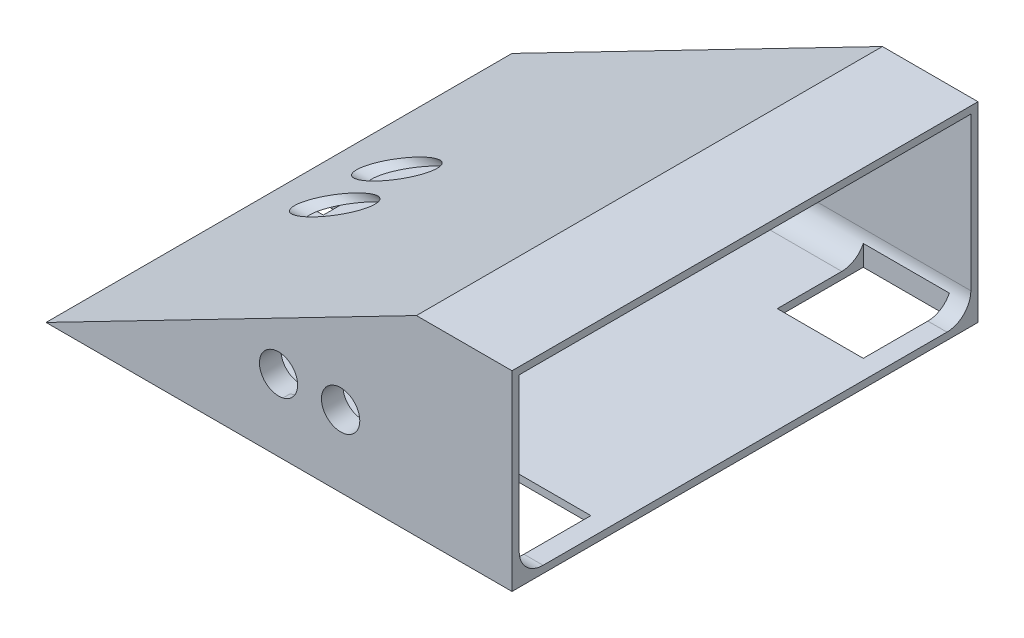
SolidWorks part; units mm, degrees
ref_plane "Front Plane" through (0, 0, 0) normal (0, 0, 1) x (1, 0, 0)
ref_plane "Top Plane" through (0, 0, 0) normal (0, 1, 0) x (1, 0, 0)
ref_plane "Right Plane" through (0, 0, 0) normal (1, 0, 0) x (0, 0, -1)
ref_plane "Plane1" through (0, 0, 0) normal (1, 0, 0) x (0, 0, -1)
ref_plane "Plane2" through (0, 0, 97.5) normal (0, 0, 1) x (1, 0, 0)
ref_plane "Plane3" through (75, 0, 0) normal (1, 0, 0) x (0, 0, -1)
sketch "Sketch2" plane through (0, 0, 0) normal (0, 0, 1) x (1, 0, 0)
  line L0 (0, 0) -> (195, 0)
  line L1 (195, 0) -> (195, 80)
  line L2 (195, 80) -> (155, 80)
  line L3 (155, 80) -> (0, 0)
  dimension "D1" = 195
  dimension "D2" = 40
  dimension "80" = 80
extrude "Robot" add sketch "Sketch2" along normal blind 195
sketch "Sketch3" plane through (0, 0, 195) normal (0, 0, 1) x (1, 0, 0)
  line L0 (0, 0) -> (195, 0) construction
  circle A0 centre (97.2899, 30) radius 8.02
  circle A1 centre (123.2899, 30) radius 8.02
  dimension "D1" = 30
  dimension "D2" = 16.04
  dimension "D4" = 16.04
  dimension "D3" = 26
  dimension "D5" = 30
sketch "Arriba" plane through (0, 80, 0) normal (0, 1, 0) x (1, 0, 0)
  line L0 (195, 0) -> (195, -195) construction
  line L1 (0, 0) -> (0, -195) construction
  line L2 (0, -97.5) -> (195, -97.5) construction
  line L3 (0, 0) -> (195, 0) construction
  line L4 (0, -195) -> (195, -195) construction
  line L5 (97.5, 0) -> (97.5, -195) construction
sketch "Adelante" plane through (0, 0, 0) normal (1, 0, 0) x (0, 0, -1)
  line L0 (0, 80) -> (0, 0) construction
  line L1 (-97.5, 80) -> (-97.5, 0) construction
  line L2 (0, 80) -> (-195, 80) construction
  line L3 (-195, 0) -> (0, 0) construction
  line L4 (-195, 80) -> (-195, 0) construction
  line L5 (0, 0) -> (-195, 0) construction
sketch "Sketch9" plane through (0, 0, 0) normal (0, 0, -1) x (-1, 0, 0)
  line L1 (0, 0) -> (-195, 0) construction
  circle A0 centre (-97.284, 30) radius 8.2
  circle A1 centre (-123.284, 30) radius 8.2
  dimension "D2" = 16.4
  dimension "D4" = 30
  dimension "D6" = 16.4
  dimension "D3" = 30
  dimension "D5" = 26
sketch "Sketch10" plane through (0, 0, 0) normal (0, -1, 0) x (-1, 0, 0)
  line L0 (0, -195) -> (-195, -195) construction
  line L1 (-187, -191) -> (-150, -191)
  line L2 (-187, -191) -> (-187, -154)
  line L3 (-187, -154) -> (-150, -154)
  line L4 (-150, -191) -> (-150, -154)
  line L5 (-195, 0) -> (-195, -195) construction
  dimension "D1" = 4
  dimension "D2" = 8
  dimension "D3" = 37
  dimension "D4" = 37
sketch "Sketch12" plane through (0, 0, 0) normal (0, -1, 0) x (-1, 0, 0)
  line L0 (-195, 0) -> (-195, -195) construction
  line L1 (-187, -40) -> (-151, -40)
  line L2 (-187, -40) -> (-187, -4)
  line L3 (-187, -4) -> (-151, -4)
  line L4 (-151, -40) -> (-151, -4)
  line L5 (0, 0) -> (-195, 0) construction
  dimension "D1" = 8
  dimension "D2" = 4
  dimension "D3" = 36
  dimension "D4" = 36
sketch "Sketch13" plane through (0, 0, 0) normal (0, -1, 0) x (1, 0, 0)
  line L0 (0, 0) -> (195, 0) construction
  line L1 (15, 8) -> (22.1, 8)
  line L2 (15, 8) -> (15, 15.1)
  line L3 (15, 15.1) -> (22.1, 15.1)
  line L4 (22.1, 8) -> (22.1, 15.1)
  line L5 (0, 0) -> (0, 195) construction
  dimension "D1" = 8
  dimension "D2" = 15
  dimension "D3" = 7.1
  dimension "D4" = 7.1
sketch "Sketch14" plane through (0, 0, 0) normal (0, -1, 0) x (-1, 0, 0)
  line L0 (0, -195) -> (-195, -195) construction
  line L1 (-15, -179.9) -> (-22.1, -179.9)
  line L2 (-15, -179.9) -> (-15, -187)
  line L3 (-15, -187) -> (-22.1, -187)
  line L4 (-22.1, -179.9) -> (-22.1, -187)
  line L5 (0, 0) -> (0, -195) construction
  dimension "D1" = 8
  dimension "D2" = 15
  dimension "D3" = 7.1
  dimension "D4" = 7.1
sketch "Sketch15" plane through (0, 0, 0) normal (0, -1, 0) x (-1, 0, 0)
  line L0 (0, -97.5) -> (-195, -97.5) construction
  line L1 (-15, -93.95) -> (-22.1, -93.95)
  line L2 (-15, -93.95) -> (-15, -101.05)
  line L3 (-15, -101.05) -> (-22.1, -101.05)
  line L4 (-22.1, -93.95) -> (-22.1, -101.05)
  line L5 (0, 0) -> (0, -195) construction
  dimension "D1" = 3.55
  dimension "D2" = 3.55
  dimension "D3" = 7.1
  dimension "D4" = 15
shell "Vacio por dentro 3mm" thickness 3 removed face at (195, 40, 97.5)
extrude "Ultrasonico Derecha" cut sketch "Sketch3" against normal blind 3
sketch "Ultrasonico Centro " plane through (0, 0, 0) normal (1, 0, 0) x (0, 0, -1)
  line L0 (0, 0) -> (-195, 0) construction
  line L1 (-97.5, 80) -> (-97.5, 0) construction
  circle A0 centre (-85, 19) radius 8.7
  circle A1 centre (-111, 19) radius 8.7
  dimension "D2" = 17.4
  dimension "D4" = 17.4
  dimension "D1" = 19
  dimension "D3" = 12.5
  dimension "D5" = 13.5
  dimension "D6" = 19
extrude "Ultrasonico Izquierda" cut sketch "Sketch9" against normal blind 3
extrude "Rueda Derecha" cut sketch "Sketch10" against normal blind 3
extrude "Rueda Izquierda" cut sketch "Sketch12" against normal blind 3
extrude "Cyn70 Derecha" cut sketch "Sketch14" against normal blind 4
extrude "Cny70 Centro" cut sketch "Sketch15" against normal blind 4
extrude "Cny70 Izquierda" cut sketch "Sketch13" against normal blind 4
extrude "Cut-Extrude4" cut sketch "Ultrasonico Centro " along normal blind 75
fillet "Fillet2" radius 10 2 edges at (103.6768, 3, 3) (103.6768, 3, 192)
sketch "Sketch16" plane through (0, 0, 195) normal (0, 0, 1) x (1, 0, 0)
  circle A0 centre (123.2899, 30) radius 8.02
  circle A1 centre (123.2899, 30) radius 8.6857
  circle A2 centre (97.3351, 30.0107) radius 8.6857
  circle A3 centre (97.3351, 30.0107) radius 8.02
extrude "Boss-Extrude1" add sketch "Sketch16" against normal blind 9
mirror "Mirror1" about plane through (0, 0, 97.5) normal (0, 0, 1) of "Boss-Extrude1"
